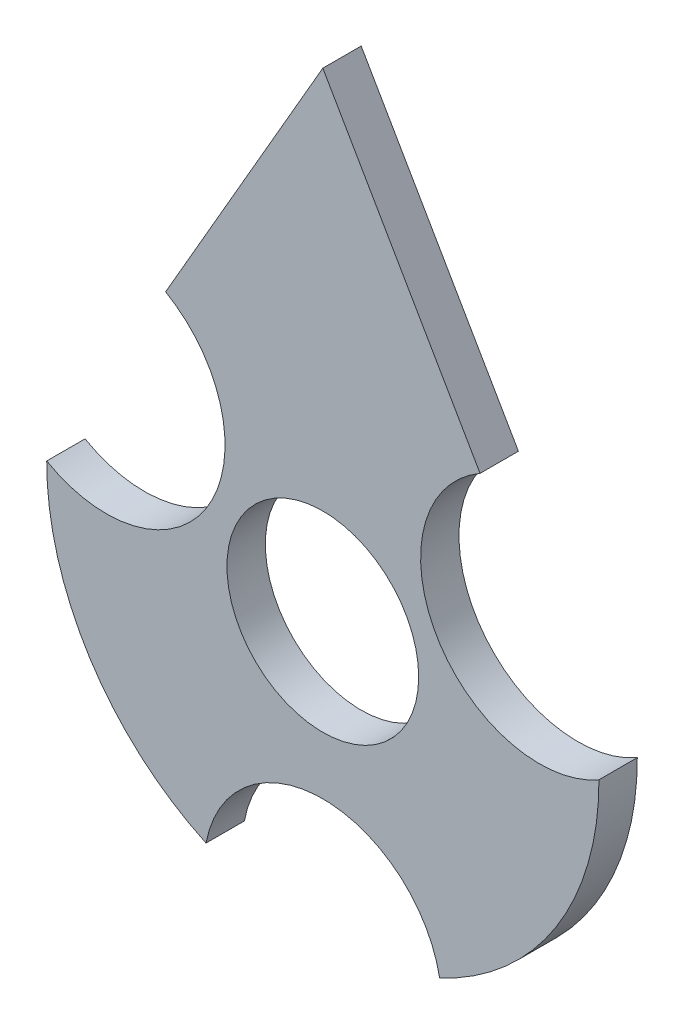
SolidWorks part; units mm, degrees
ref_plane "Front Plane" through (0, 0, 0) normal (0, 0, 1) x (1, 0, 0)
ref_plane "Top Plane" through (0, 0, 0) normal (0, 1, 0) x (1, 0, 0)
ref_plane "Right Plane" through (0, 0, 0) normal (1, 0, 0) x (0, 0, -1)
sketch "Sketch1" plane through (0, 0, 0) normal (0, 0, 1) x (1, 0, 0)
  line L0 (0, 0) -> (0, 50000) construction
  line L1 (0, 0) -> (50000, 0) construction
  line L2 (0, 125) -> (41, 53.9859)
  line L3 (0, 125) -> (-41, 53.9859)
  circle A0 centre (0, 0) radius 25
  arc A1 (41, 53.9859) -> (71.9994, 0.292) centre (56.5, 27.1391) ccw
  arc A2 (30.4601, -65.2394) -> (-30.4601, -65.2394) centre (0, -71) ccw
  arc A3 (-41, 53.9859) -> (-71.9994, 0.292) centre (-56.5, 27.1391) cw
  arc A4 (30.4601, -65.2394) -> (71.9994, 0.292) centre (0, 0) ccw
  arc A5 (-30.4601, -65.2394) -> (-71.9994, 0.292) centre (0, 0) cw
  point P8 (0, 0)
  point P10 (0, 0)
  point P14 (0, 0)
  point P17 (0, 0)
  point P18 (0, 0)
  point P23 (0, 0)
  dimension "D1" = 50
  dimension "D2" = 62
  dimension "D3" = 62
  dimension "D7" = 196
  dimension "D8" = 72
  dimension "D4" = 60
  dimension "D5" = 125
  dimension "D6" = 113
extrude "Boss-Extrude1" [suppressed] add sketch "Sketch1" along normal mid plane 10
extrude "Boss-Extrude3" add sketch "Sketch1<6>" along normal mid plane 10
sketch "Sketch1<6>" plane through (0, 0, 0) normal (0, 0, 1) x (1, 0, 0) same geometry as "Sketch1"
